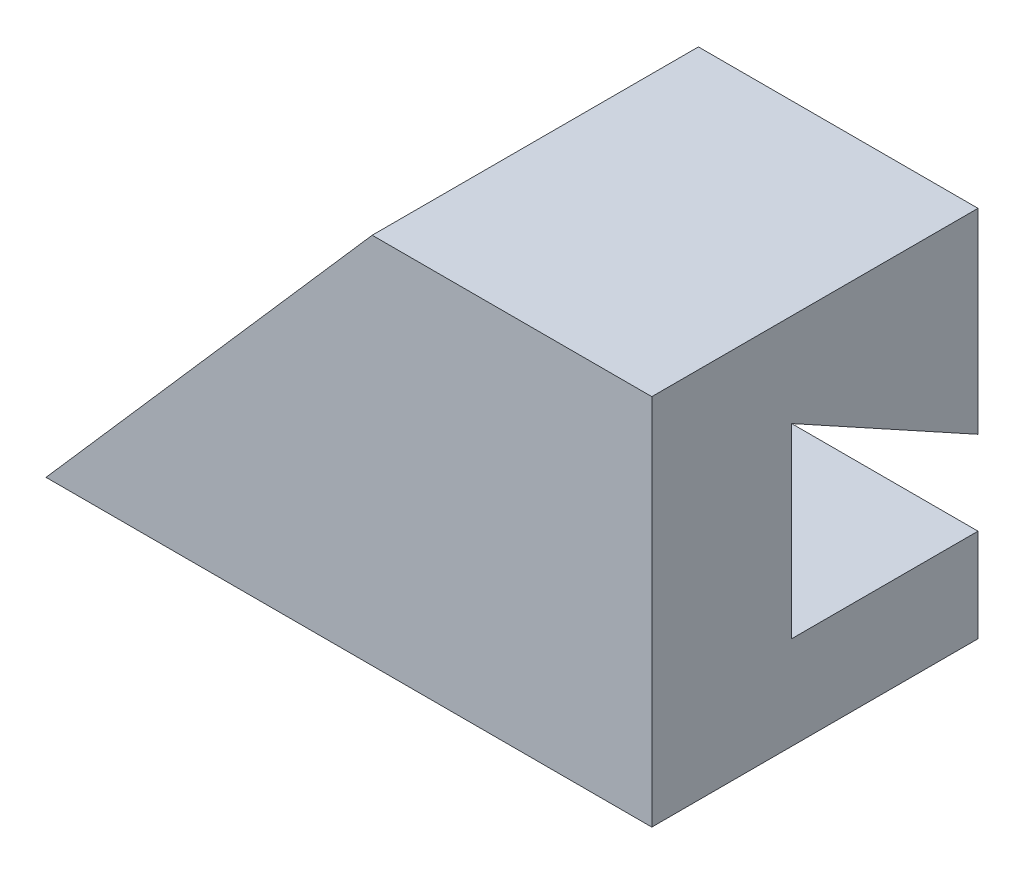
SolidWorks part; units mm, degrees
ref_plane "Plan de face" through (0, 0, 0) normal (0, 0, 1) x (1, 0, 0)
ref_plane "Plan de dessus" through (0, 0, 0) normal (0, 1, 0) x (1, 0, 0)
ref_plane "Plan de droite" through (0, 0, 0) normal (1, 0, 0) x (0, 0, -1)
sketch "Esquisse1" plane through (0, 0, 0) normal (1, 0, 0) x (0, 0, -1)
  line L0 (-21.2047, -24.0631) -> (13.7953, -24.0631)
  line L1 (13.7953, -24.0631) -> (13.7953, -14.0631)
  line L2 (13.7953, -14.0631) -> (-6.2047, -14.0631)
  line L3 (-6.2047, -14.0631) -> (-6.2047, 5.9369)
  line L4 (-6.2047, 5.9369) -> (13.7953, -5.0631)
  line L5 (13.7953, -5.0631) -> (13.7953, 15.9369)
  line L6 (13.7953, 15.9369) -> (-21.2047, 15.9369)
  line L7 (-21.2047, 15.9369) -> (-21.2047, -24.0631)
  dimension "D1" = 35
  dimension "D2" = 10
  dimension "D3" = 20
  dimension "D4" = 40
  dimension "D5" = 20
  dimension "D6" = 35
  dimension "D7" = 21
extrude "Boss.-Extru.1" add sketch "Esquisse1" along normal blind 65
chamfer "Chanfrein1" distance 40 distance2 35 1 edges at (0, 15.9369, 3.7047) first distance on face at (0, -5.4381, -0.0453)
